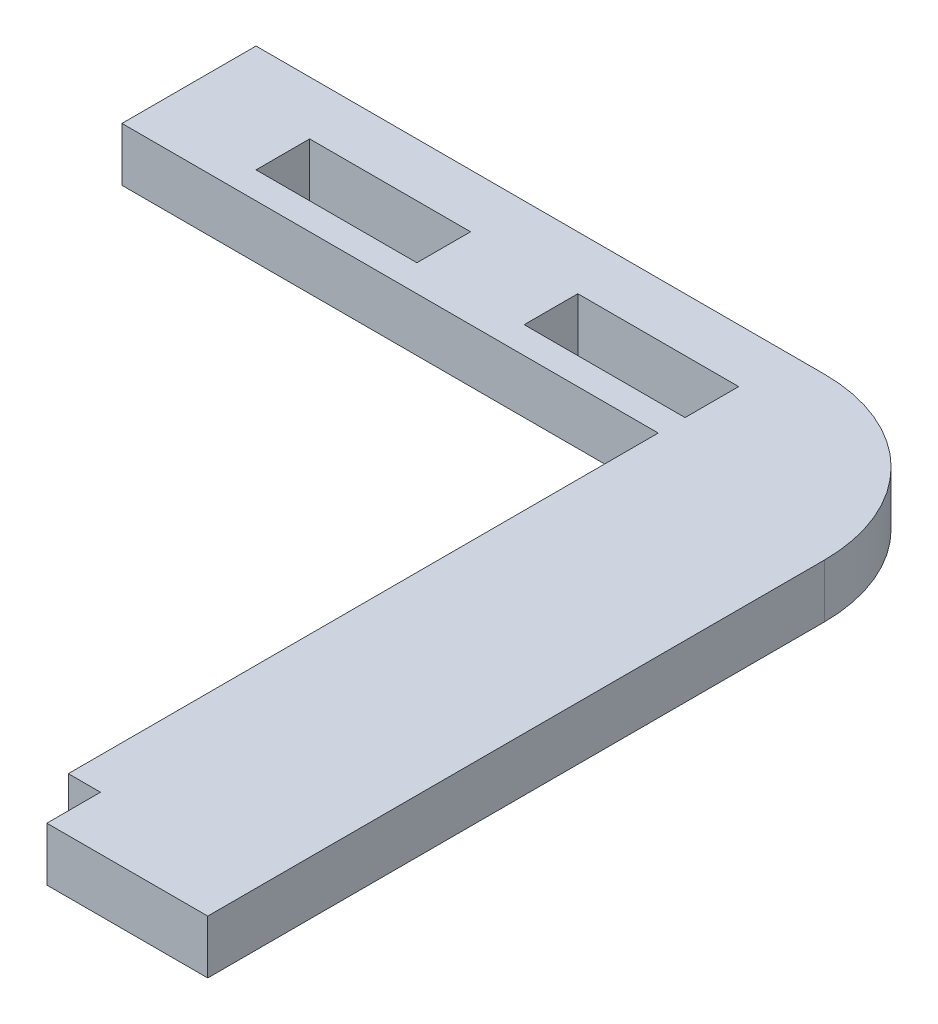
SolidWorks part; units mm, degrees
ref_plane "Front Plane" through (0, 0, 0) normal (0, 0, 1) x (1, 0, 0)
ref_plane "Top Plane" through (0, 0, 0) normal (0, 1, 0) x (1, 0, 0)
ref_plane "Right Plane" through (0, 0, 0) normal (1, 0, 0) x (0, 0, -1)
sketch "Sketch1" plane through (0, 0, 0) normal (0, 1, 0) x (1, 0, 0)
  line L0 (-34, -17.5) -> (-37, -17.5)
  line L4 (-37, -17.5) -> (-37, 37.5)
  line L6 (-34, -17.5) -> (-34, -22.5)
  line L7 (-34, -22.5) -> (-19, -22.5)
  line L9 (-19, 50) -> (-87, 50)
  line L11 (-37, 37.5) -> (-87, 37.5)
  line L12 (-87, 50) -> (-87, 37.5)
  line L13 (-77, 40) -> (-62, 40)
  line L14 (-77, 40) -> (-77, 45)
  line L15 (-77, 45) -> (-62, 45)
  line L16 (-62, 40) -> (-62, 45)
  line L17 (-19, 50) -> (-19, -22.5)
  line L19 (-52, 40) -> (-37, 40)
  line L20 (-52, 40) -> (-52, 45)
  line L21 (-52, 45) -> (-37, 45)
  line L22 (-37, 40) -> (-37, 45)
  point P12 (-87, 43.75)
  point P17 (-52, 42.5)
  dimension "D2" = 3
  dimension "D3" = 15
  dimension "D4" = 55
  dimension "D5" = 12.5
  dimension "D6" = 50
  dimension "D7" = 10
  dimension "D8" = 2.5
  dimension "D9" = 5
  dimension "D10" = 15
  dimension "D11" = 5
  dimension "D12" = 10
  dimension "D13" = 15
extrude "Boss-Extrude1" add sketch "Sketch1" along normal blind 5
fillet "Fillet3" radius 15 1 edges at (-19, 2.5, -50)
